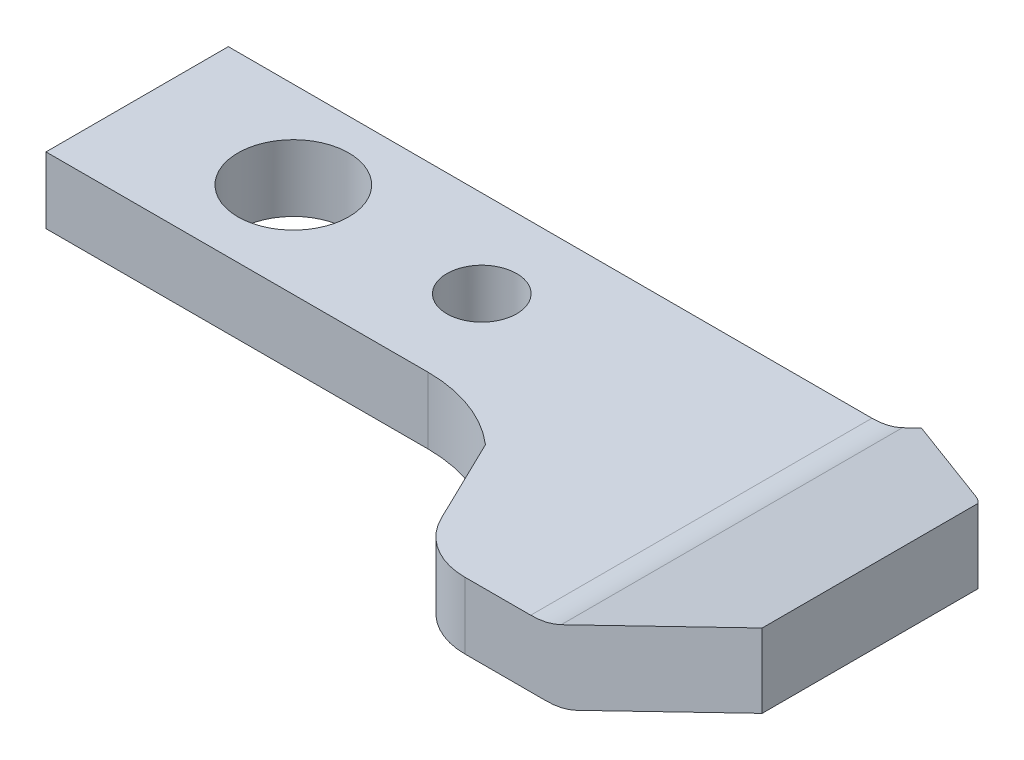
SolidWorks part; units mm, degrees
material "AISI 1020"
ref_plane "Alzado" through (0, 0, 0) normal (0, 0, 1) x (1, 0, 0)
ref_plane "Planta" through (0, 0, 0) normal (0, 1, 0) x (1, 0, 0)
ref_plane "Vista lateral" through (0, 0, 0) normal (1, 0, 0) x (0, 0, -1)
sketch "Croquis1" plane through (0, 0, 0) normal (0, 0, 1) x (-1, 0, 0)
  line L0 (197, -27.53) -> (93.2952, -27.53)
  line L2 (93.2952, -27.53) -> (56.242, -9.53)
  line L4 (0, 0) -> (58.4343, 0)
  line L5 (197, -27.53) -> (197, -18)
  line L6 (0, 0) -> (0, -9.53)
  line L7 (0, -9.53) -> (56.242, -9.53)
  line L8 (197, -18) -> (95.4875, -18)
  line L9 (95.4875, -18) -> (58.4343, 0)
  line L10 (95.4875, -18) -> (60.4062, -0.9579) construction
  line L12 (0, 25) -> (58.5827, 25)
  line L13 (1018.7132, -27.53) -> (93.2952, -27.53) construction
  line L14 (1018.7132, -18) -> (95.4875, -18) construction
  point P2 (0, -4.765)
  dimension "D1" = 9.53
  dimension "D3" = 25
  dimension "D4" = 197
  dimension "D5" = 103.7048
  dimension "D6" = 37.0532
  dimension "D7" = 18
  dimension "D8" = 58.5827
  dimension "D2" = 9.53
extrude "Saliente-Extruir1" add sketch "Croquis1" along normal blind 100 contours L8 L9 L4 L6 L7 L2 L0 L5 region at (-145.1476, 25.5409, 0)
sketch "Croquis4" plane through (0, 18, 0) normal (0, -1, 0) x (1, 0, 0)
  line L0 (-135.2991, 26.0913) -> (-190.012, 26.1261)
  line L2 (-208.4085, -39.0201) -> (-31.9322, -39.0201) construction
  line L3 (-190.012, -1.657) -> (-96.2087, -1.657)
  line L4 (-190.012, 26.1261) -> (-190.012, -1.657)
  line L5 (-89.3086, 48.8915) -> (-107.2415, 48.8915)
  line L6 (-21.1529, 65.7945) -> (-64.626, 17.9723)
  line L8 (-172.3293, 28.877) -> (-190.012, 28.877)
  line L9 (-301.2213, -1.3807) -> (-231.0539, -1.3807) construction
  line L10 (-301.2213, 0.6193) -> (-231.4748, 0.6193)
  line L11 (-49.1319, 94.291) -> (-122.188, 30.9774)
  line L13 (-116.2408, 43.2518) -> (-122.188, 30.9774)
  line L14 (-80.9781, 6.5715) -> (-108.7778, -12.2303) construction
  line L15 (-66.4232, 16.4155) -> (-90.6064, 0.0596)
  circle A1 centre (-35.952, 79.2477) radius 20
  arc A3 (-64.626, 17.9723) -> (-66.4232, 16.4155) centre (-72.0255, 24.6989) cw
  circle A4 centre (-87.5623, 29.8614) radius 146.8534
  arc A11 (-135.2991, 26.0913) -> (-122.188, 30.9774) centre (-135.2864, 46.0913) ccw
  circle A14 centre (-155.012, 13.5358) radius 5
  circle A15 centre (-182.012, 13.5358) radius 5
  arc A16 (-96.2087, -1.657) -> (-90.6064, 0.0596) centre (-96.2087, 8.343) ccw
  arc A17 (-55.2498, 84.5004) -> (-85.3149, 49.7236) centre (-106.5468, 98.4632) cw
  arc A18 (-107.2415, 48.8915) -> (-116.2408, 43.2518) centre (-107.2415, 38.8915) ccw
  arc A19 (-85.3149, 49.7236) -> (-89.3086, 48.8915) centre (-89.3086, 58.8915) cw
  line M1 (-197, 0) -> (-95.4875, 0)
  line M2 (-95.4875, 0) -> (-95.4875, 100)
  line M3 (-95.4875, 100) -> (-197, 100)
  line M4 (-197, 100) -> (-197, 0)
  dimension "D1" = 10
  dimension "D2" = 10
extrude "Cortar-Extruir3" cut sketch "Croquis4" against normal through all both and the other way through all contours A4 M2 M1 M4 M3 | L11 L5 M2 region at (-150.4879, 18, 63.8487) region at (-97.4974, 18, 50.6334) region at (-73.2831, 18, -112.1221)
sketch "Croquis5" plane through (0, 0, 0) normal (0, -1, 0) x (1, 0, 0)
  circle A1 centre (-35.952, 79.2477) radius 6
  dimension "D1" = 12
extrude "Cortar-Extruir4" cut sketch "Croquis5" against normal through all both and the other way through all
sketch "Croquis6" plane through (0, 18, 0) normal (0, -1, 0) x (1, 0, 0)
  circle A0 centre (-168.1955, 12.5) radius 5 construction
  circle A1 centre (-141.1955, 12.5) radius 5 construction
  circle A2 centre (-168.1955, 12.5) radius 5
  circle A3 centre (-141.1955, 12.5) radius 5
extrude "Cortar-Extruir5" cut sketch "Croquis6" against normal through all both and the other way through all
sketch "Croquis12" plane through (0, 0, 0) normal (0, -1, 0) x (1, 0, 0)
  circle A0 centre (-35.952, 79.2477) radius 6 construction
  circle A1 centre (-35.952, 79.2477) radius 6
  circle A2 centre (-35.952, 79.2477) radius 8
  dimension "D1" = 16
extrude "Saliente-Extruir5" add sketch "Croquis12" along normal blind 15.13
ref_plane "Plano1" through (0, -14.13, 0) normal (0, -1, 0) x (-1, 0, 0)
sketch "Croquis14" plane through (0, -14.13, 0) normal (0, -1, 0) x (-1, 0, 0)
  circle A0 centre (35.952, -79.2477) radius 10
  circle A1 centre (35.952, -79.2477) radius 6 construction
  circle A2 centre (35.952, -79.2477) radius 6
  dimension "D1" = 20
extrude "Saliente-Extruir6" add sketch "Croquis14" against normal up to surface (14.13 mm away) up to face at (-45.3035, 0, 68.1226)
fillet "Redondeo1" radius 10 4 edges at (-95.4875, 18, 24.4458) (-58.4343, 0, 50.3149) (-93.2952, 27.53, 24.4458) (-56.242, 9.53, 54.2302)
ref_plane "Plano2" through (0, -82, 0) normal (0, -1, 0) x (-1, 0, 0)
mirror "Simetría1" about plane through (0, -82, 0) normal (0, -1, 0) of bodies 111
sketch "Croquis15" plane through (0, -82, 0) normal (0, -1, 0) x (-1, 0, 0)
  circle A0 centre (137.5464, -18.6224) radius 129.914
extrude "Cortar-Extruir6" cut sketch "Croquis15" against normal through all
sketch "Croquis16" plane through (0, -82, 0) normal (0, -1, 0) x (-1, 0, 0)
  line L1 (64.626, -48.8915) -> (64.626, 8.4332)
  line L3 (217.4594, -48.8915) -> (217.4594, 8.4332)
  line L4 (217.4594, 8.4332) -> (64.626, 8.4332)
  line L5 (95.5956, -48.8915) -> (107.2415, -48.8915) construction
  line L6 (64.626, -48.8915) -> (217.4594, -48.8915)
  circle A0 centre (140.265, -47.2698) radius 167.8189
extrude "Cortar-Extruir7" cut sketch "Croquis16" against normal through all both and the other way through all
sketch "Croquis3" plane through (0, 18, 0) normal (0, -1, 0) x (-1, 0, 0)
  line L0 (106.9883, -8.8264) -> (106.9883, -24.5143)
  line L2 (86.9883, -44.5143) -> (26.5762, -44.5143)
  line L3 (26.5762, -94.5143) -> (146.9883, -94.5143)
  line L4 (166.9883, -74.5143) -> (166.9883, -8.8264)
  line L5 (161.9883, -3.8264) -> (111.9883, -3.8264)
  circle A0 centre (26.5762, -69.5143) radius 189.5759
  circle A1 centre (26.5762, -69.5143) radius 8
  circle A2 centre (26.5762, -69.5143) radius 25
  arc A3 (146.9883, -94.5143) -> (166.9883, -74.5143) centre (146.9883, -74.5143) ccw
  arc A4 (106.9883, -24.5143) -> (86.9883, -44.5143) centre (86.9883, -24.5143) cw
  arc A5 (166.9883, -8.8264) -> (161.9883, -3.8264) centre (161.9883, -8.8264) ccw
  arc A6 (106.9883, -8.8264) -> (111.9883, -3.8264) centre (111.9883, -8.8264) cw
  dimension "D1" = 50
  dimension "D4" = 20
  dimension "D5" = 5
  dimension "D2" = 16
  dimension "D3" = 60
sketch "Croquis17" plane through (0, 0, 0) normal (0, 1, 0) x (1, 0, 0)
  circle A0 centre (-168.1955, -12.5) radius 7.94
  dimension "D1" = 15.88
extrude "Cortar-Extruir8" cut sketch "Croquis17" against normal through all
